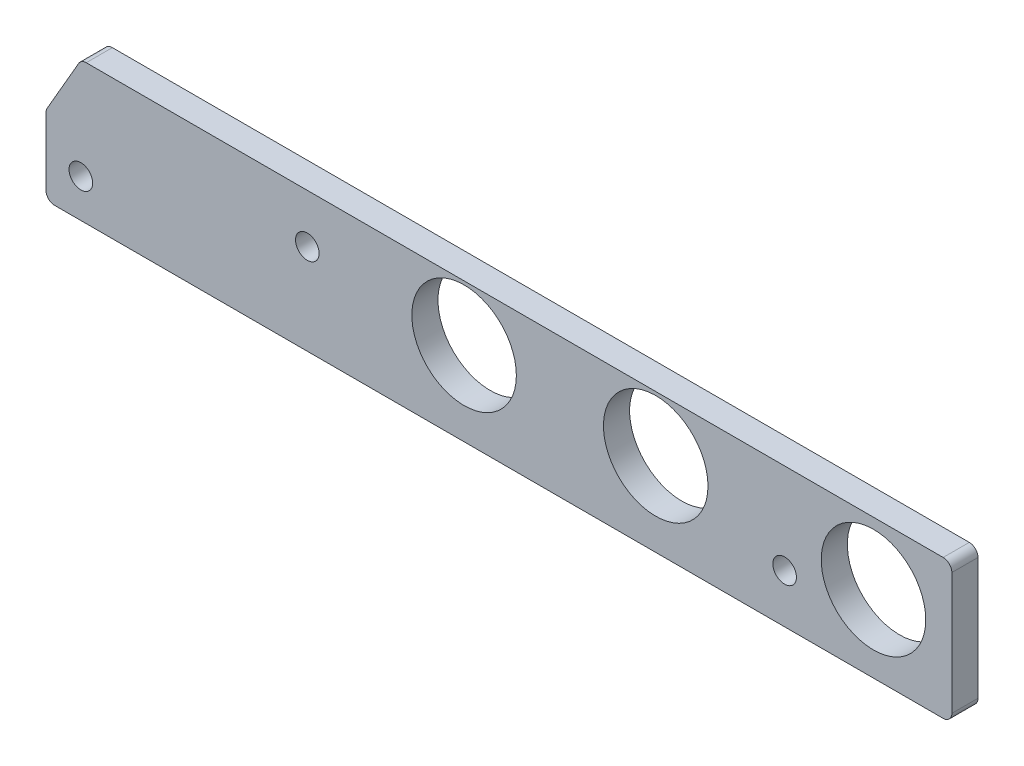
SolidWorks part; units mm, degrees
material "Acrylic (Medium-high impact)"
ref_plane "Front Plane" through (0, 0, 0) normal (0, 0, 1) x (1, 0, 0)
ref_plane "Top Plane" through (0, 0, 0) normal (0, 1, 0) x (1, 0, 0)
ref_plane "Right Plane" through (0, 0, 0) normal (1, 0, 0) x (0, 0, -1)
sketch "Sketch1" plane through (0, 0, 0) normal (0, 0, 1) x (1, 0, 0)
  line L5 (-159.1425, -0.7937) -> (-164.8873, -10.7441)
  line L6 (-165.1, -11.5379) -> (-165.1, -23.8125)
  line L7 (-163.5125, -25.4) -> (-1.5875, -25.4)
  line L8 (0, -23.8125) -> (0, -1.5875)
  line L9 (-1.5875, 0) -> (-157.7677, 0)
  line L10 (-159.1425, -0.7937) -> (-164.8873, -10.7441)
  line L11 (-165.1, -11.5379) -> (-165.1, -23.8125)
  line L12 (-163.5125, -25.4) -> (-1.5875, -25.4)
  line L13 (0, -23.8125) -> (0, -1.5875)
  line L14 (-1.5875, 0) -> (-157.7677, 0)
  arc A5 (-157.7677, 0) -> (-159.1425, -0.7937) centre (-157.7677, -1.5875) ccw
  arc A6 (-164.8873, -10.7441) -> (-165.1, -11.5379) centre (-163.5125, -11.5379) ccw
  arc A7 (-165.1, -23.8125) -> (-163.5125, -25.4) centre (-163.5125, -23.8125) ccw
  arc A8 (-1.5875, -25.4) -> (0, -23.8125) centre (-1.5875, -23.8125) ccw
  arc A9 (0, -1.5875) -> (-1.5875, 0) centre (-1.5875, -1.5875) ccw
  arc A10 (-157.7677, 0) -> (-159.1425, -0.7937) centre (-157.7677, -1.5875) ccw
  arc A11 (-164.8873, -10.7441) -> (-165.1, -11.5379) centre (-163.5125, -11.5379) ccw
  arc A12 (-165.1, -23.8125) -> (-163.5125, -25.4) centre (-163.5125, -23.8125) ccw
  arc A13 (-1.5875, -25.4) -> (0, -23.8125) centre (-1.5875, -23.8125) ccw
  arc A14 (0, -1.5875) -> (-1.5875, 0) centre (-1.5875, -1.5875) ccw
  dimension "D1" = 0
extrude "Boss-Extrude1" add sketch "Sketch1" along normal blind 4.7625
hole_wizard "#6 Clearance Hole1" positions "Sketch5" profile "Sketch4" hole size "#6" standard "ANSI Inch" end condition through all
sketch "Sketch5" plane through (0, 0, 4.7625) normal (0, 0, 1) x (1, 0, 0)
  point P0 (-158.75, -18.415)
  point P3 (-117.475, -8.89)
  point P6 (-30.48, -16.51)
sketch "Sketch4" plane through (-158.75, -18.415, 4.7625) normal (1, 0, 0) x (0, -1, 0)
  line L0 (0, 0) -> (0, 4.7625)
  line L1 (0, 4.7625) -> (2.1526, 4.7625)
  line L2 (2.1526, 4.7625) -> (2.1526, 0)
  line L5 (2.1526, 0) -> (0, 0)
  line L11 (0, -6.35) -> (0, 107.95) construction
  dimension "Thru Hole Dia." = 4.3053
  dimension "Thru Hole Depth" = 4.7625
hole_wizard "3/4 (0.75) Diameter Hole1" positions "Sketch7" profile "Sketch6" hole size "3/4" standard "ANSI Inch" end condition through all
sketch "Sketch7" plane through (0, 0, 4.7625) normal (0, 0, 1) x (1, 0, 0)
  point P0 (-88.9, -10.16)
  point P3 (-53.975, -10.16)
  point P6 (-14.2875, -11.43)
sketch "Sketch6" plane through (-88.9, -10.16, 4.7625) normal (1, 0, 0) x (0, -1, 0)
  line L0 (0, 0) -> (0, 4.7625)
  line L1 (0, 4.7625) -> (9.525, 4.7625)
  line L2 (9.525, 4.7625) -> (9.525, 0)
  line L5 (9.525, 0) -> (0, 0)
  line L11 (0, -6.35) -> (0, 107.95) construction
  dimension "Thru Hole Dia." = 19.05
  dimension "Thru Hole Depth" = 4.7625
